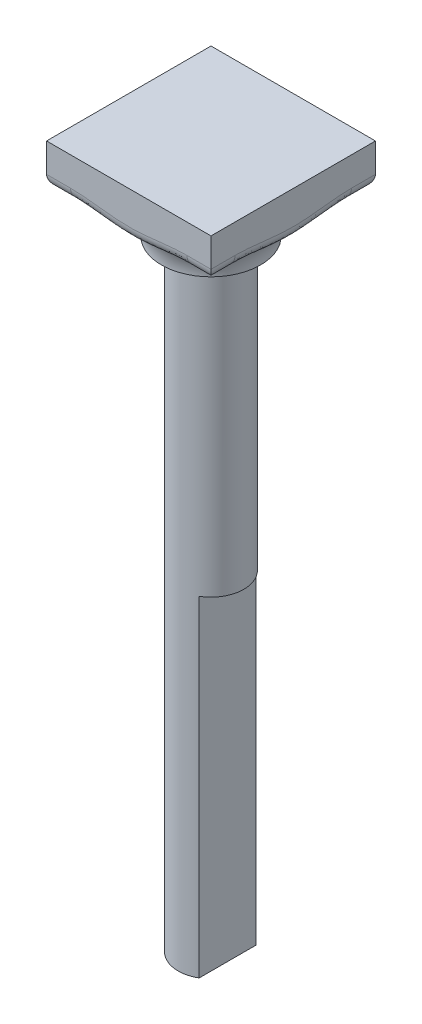
SolidWorks part; units mm, degrees
ref_plane "Alzado" through (0, 0, 0) normal (0, 0, 1) x (1, 0, 0)
ref_plane "Planta" through (0, 0, 0) normal (0, 1, 0) x (1, 0, 0)
ref_plane "Vista lateral" through (0, 0, 0) normal (1, 0, 0) x (0, 0, -1)
sketch "Croquis1" plane through (0, 0, 0) normal (1, 0, 0) x (0, 0, -1)
  line L0 (0, 0) -> (0, 19394.6636) construction
  line L1 (0, 0) -> (-3.975, 0)
  line L2 (-3.975, 0) -> (-3.975, 75)
  line L3 (-3.975, 75) -> (-6, 75)
  line L4 (-6, 75) -> (-6, 80)
  line L5 (-6, 80) -> (0, 80)
  line L6 (0, 80) -> (0, 0)
  dimension "D1" = 75
  dimension "D2" = 5
  dimension "D3" = 6
  dimension "D4" = 3.975
revolve "Revolución1" add sketch "Croquis1" angle 360 about L0
sketch "Croquis2" plane through (0, 80, 0) normal (0, 1, 0) x (1, 0, 0)
  line L5 (-9.95, -9.95) -> (9.95, -9.95)
  line L6 (-9.95, -9.95) -> (-9.95, 9.95)
  line L7 (-9.95, 9.95) -> (9.95, 9.95)
  line L8 (9.95, -9.95) -> (9.95, 9.95)
  line L9 (-9.95, -9.95) -> (9.95, 9.95) construction
  line L10 (-9.95, 9.95) -> (9.95, -9.95) construction
  point P0 (0, 0)
  dimension "D1" = 19.9
extrude "Saliente-Extruir1" add sketch "Croquis2" along normal blind 5 contours L5 L8 L7 L6
sketch "Croquis3" plane through (0, 0, 0) normal (0, -1, 0) x (1, 0, 0)
  line L0 (2, 3.4352) -> (2, -3.4352)
  line L1 (0, 0) -> (2, 0) construction
  circle A0 centre (0, 0) radius 3.975 construction
  dimension "D1" = 2
extrude "Cortar-Extruir1" cut sketch "Croquis3" against normal blind 40 and the other way through all
fillet "Redondeo3" radius 5 1 edges at (0, 80, -6)
fillet "Redondeo4" radius 1.5 12 edges at (-7.3201, 80, 9.95) (7.3201, 80, 9.95) (9.95, 80, 7.3201) (9.95, 80, -7.3201) (-7.3201, 80, -9.95) (7.3201, 80, -9.95) (-9.95, 80, 7.3201) (-9.95, 80, -7.3201) (9.95, 79.8885, 0) (0, 79.8885, -9.95) (-9.95, 79.8885, 0) (0, 79.8885, 9.95)
